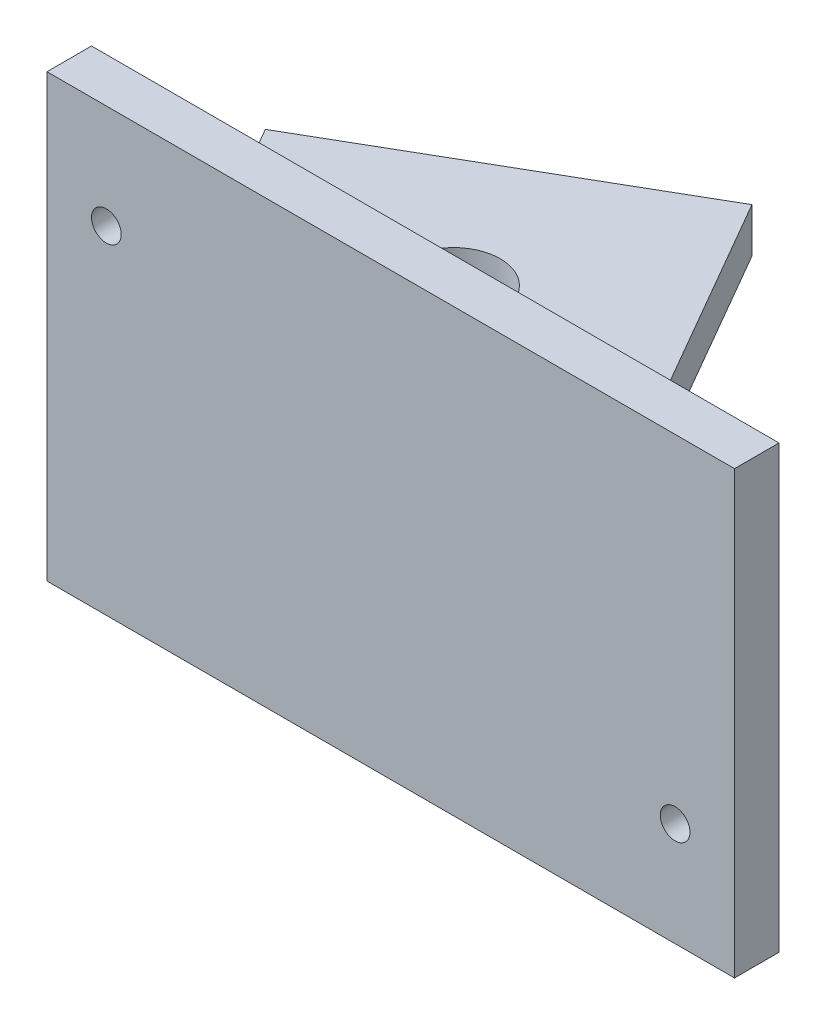
SolidWorks part; units mm, degrees
ref_plane "Front Plane" through (0, 0, 0) normal (0, 0, 1) x (1, 0, 0)
ref_plane "Top Plane" through (0, 0, 0) normal (0, 1, 0) x (1, 0, 0)
ref_plane "Right Plane" through (0, 0, 0) normal (1, 0, 0) x (0, 0, -1)
sketch "Sketch1" plane through (0, 0, 0) normal (0, 0, 1) x (1, 0, 0)
  line L1 (0, 0) -> (33.782, 0) construction
  line L2 (0, 0) -> (0, 19.812) construction
  line L3 (0, 19.812) -> (33.782, 19.812) construction
  line L4 (33.782, 0) -> (33.782, 19.812) construction
  line L5 (-1.397, -1.397) -> (35.3695, -1.397)
  line L6 (-1.397, -1.397) -> (-1.397, 19.812)
  line L7 (-1.397, 19.812) -> (35.3695, 19.812)
  line L8 (35.3695, -1.397) -> (35.3695, 19.812)
  circle A0 centre (1.778, 14.2558) radius 0.7938
  circle A1 centre (32.1945, 1.778) radius 0.7937
  dimension "D3" = 1.5875
  dimension "D4" = 1.5875
  dimension "D5" = 1.778
  dimension "D6" = 1.5875
  dimension "D7" = 1.778
  dimension "D8" = 5.5562
  dimension "D9" = 3.175
  dimension "D11" = 3.175
  dimension "D12" = 5.5562
  dimension "D1" = 19.812
  dimension "D2" = 33.782
  dimension "D10" = 3.175
extrude "Boss-Extrude1" add sketch "Sketch1" along normal blind 2.3813
sketch "Sketch2" plane through (0, -1.397, 0) normal (0, -1, 0) x (1, 0, 0)
  line L8 (-1.397, 0) -> (20.6, 0) construction
  line L9 (-1.397, 2.3813) -> (35.3695, 2.3813)
  line L10 (-1.397, 2.3813) -> (-1.397, 0)
  line L12 (35.3695, 2.3813) -> (35.3695, 0)
  line L15 (2.4008, -31.522) -> (-14.097, -21.997)
  line L16 (-1.397, 0) -> (-14.097, -21.997)
  line L17 (2.4008, -31.522) -> (20.6, 0)
  line L18 (20.6, 0) -> (35.3695, 0)
  dimension "D1" = 19.05
  dimension "D2" = 60
  dimension "D3" = 25.4
extrude "Boss-Extrude3" add sketch "Sketch2" along normal blind 2.3813
sketch "Sketch4" plane through (0, -1.397, 0) normal (0, 1, 0) x (1, 0, 0)
  line L0 (-5.8481, 26.7595) -> (-1.8285, 19.7973) construction
  line L1 (-14.097, 21.997) -> (2.4008, 31.522) construction
  line L2 (-1.8285, 19.7973) -> (4.5215, 8.7988) construction
  line L3 (4.5215, 8.7988) -> (9.6015, 0) construction
  line L4 (-1.397, 0) -> (20.6, 0) construction
  circle A0 centre (-1.8285, 19.7973) radius 2.4892
  circle A1 centre (4.5215, 8.7988) radius 2.4892
  dimension "D1" = 4.9784
  dimension "D2" = 12.7
  dimension "D3" = 10.16
extrude "Cut-Extrude2" cut sketch "Sketch4" against normal up to next
